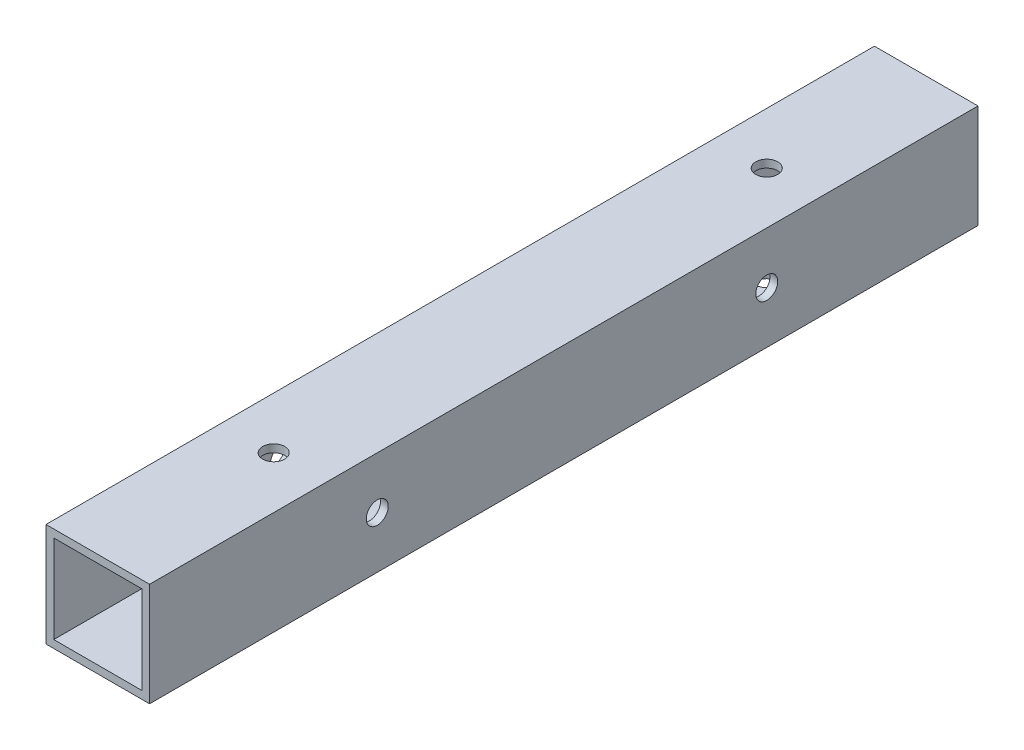
SolidWorks part; units mm, degrees
ref_plane "Front Plane" through (0, 0, 0) normal (0, 0, 1) x (1, 0, 0)
ref_plane "Top Plane" through (0, 0, 0) normal (0, 1, 0) x (1, 0, 0)
ref_plane "Right Plane" through (0, 0, 0) normal (1, 0, 0) x (0, 0, -1)
sketch "Sketch1" plane through (0, 0, 0) normal (0, 0, 1) x (1, 0, 0)
  line L0 (-8.5, -8.5) -> (8.5, -8.5)
  line L1 (-10, -10) -> (10, -10)
  line L2 (-10, -10) -> (-10, 10)
  line L3 (-10, 10) -> (10, 10)
  line L4 (10, -10) -> (10, 10)
  line L5 (-10, -10) -> (10, 10) construction
  line L6 (-10, 10) -> (10, -10) construction
  line L7 (8.5, -8.5) -> (8.5, 8.5)
  line L8 (-8.5, 8.5) -> (8.5, 8.5)
  line L9 (-8.5, -8.5) -> (-8.5, 8.5)
  point P0 (0, 0)
  dimension "D1" = 20
  dimension "D3" = 20
  dimension "D2" = 1.5
extrude "Boss-Extrude1" add sketch "Sketch1" against normal blind 160
sketch "Sketch2" plane through (0, 10, 0) normal (0, 1, 0) x (1, 0, 0)
  line L0 (10, 0) -> (-10, 0) construction
  line L1 (10, 160) -> (-10, 160) construction
  circle A0 centre (0, 33.975) radius 2.125
  circle A1 centre (0, 129.2) radius 2.125
  dimension "D1" = 4.25
  dimension "D3" = 4.25
  dimension "D2" = 33.975
  dimension "D4" = 30.8
extrude "Cut-Extrude1" cut sketch "Sketch2" against normal through all
sketch "Sketch3" plane through (-10, 0, 0) normal (-1, 0, 0) x (0, 0, 1)
  line L0 (-160, 10) -> (-160, -10) construction
  circle A0 centre (-43.975, 0) radius 2.125
  circle A1 centre (-119.2, 0) radius 2.125
  dimension "D1" = 4.25
  dimension "D3" = 4.25
  dimension "D2" = 43.975
  dimension "D4" = 40.8
extrude "Cut-Extrude2" cut sketch "Sketch3" against normal through all
